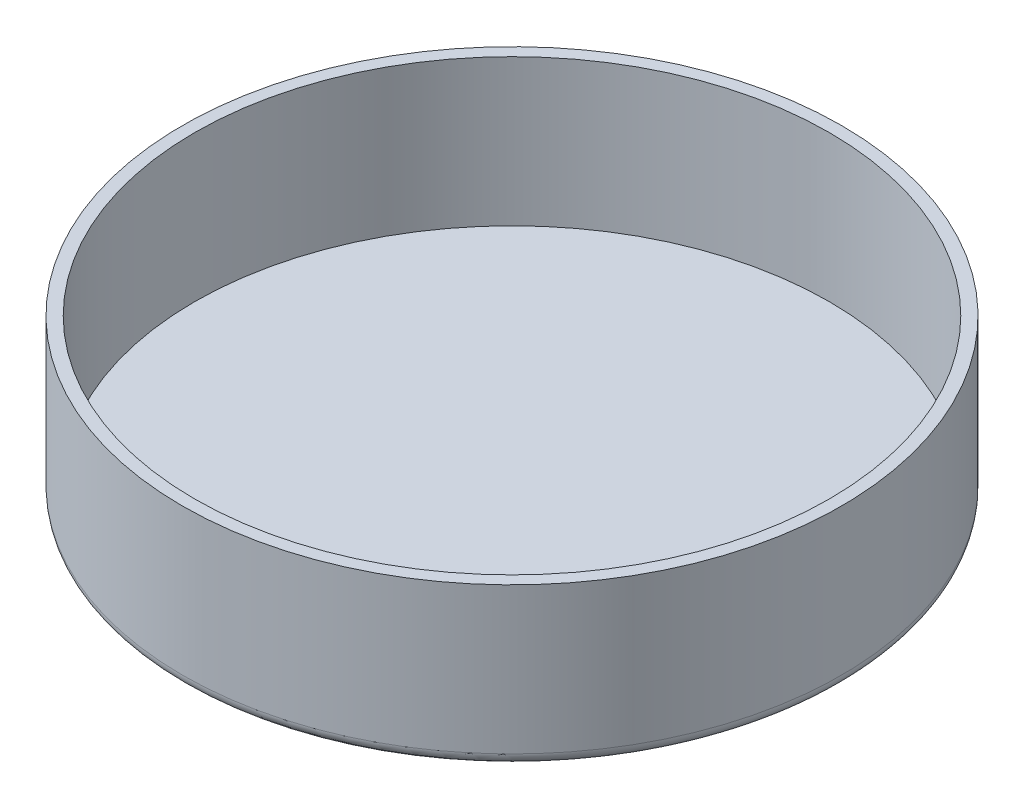
SolidWorks part; units mm, degrees
material "PS Medium/High Flow"
ref_plane "Front Plane" through (0, 0, 0) normal (0, 0, 1) x (1, 0, 0)
ref_plane "Top Plane" through (0, 0, 0) normal (0, 1, 0) x (1, 0, 0)
ref_plane "Right Plane" through (0, 0, 0) normal (1, 0, 0) x (0, 0, -1)
sketch "Sketch1" plane through (0, 0, 0) normal (0, 1, 0) x (1, 0, 0)
  circle A0 centre (0, 0) radius 26
  circle A1 centre (0, 0) radius 27
  dimension "D1" = 52
  dimension "D2" = 54
extrude "Boss-Extrude1" add sketch "Sketch1" along normal blind 12
sketch "Sketch2" plane through (0, 0, 0) normal (0, -1, 0) x (1, 0, 0)
  circle A0 centre (0, 0) radius 27
extrude "Boss-Extrude2" add sketch "Sketch2" along normal blind 1
sketch "Sketch3" plane through (0, -1, 0) normal (0, -1, 0) x (1, 0, 0)
  circle A0 centre (0, 0) radius 25.5
  circle A1 centre (0, 0) radius 24.5
  dimension "D1" = 1
  dimension "D2" = 49
extrude "Boss-Extrude3" add sketch "Sketch3" along normal blind 0.6
fillet "Fillet1" radius 1 1 edges at (0, -1, -27)
fillet "Fillet2" radius 0.5 2 edges at (0, -1.6, -24.5) (0, -1.6, -25.5)
